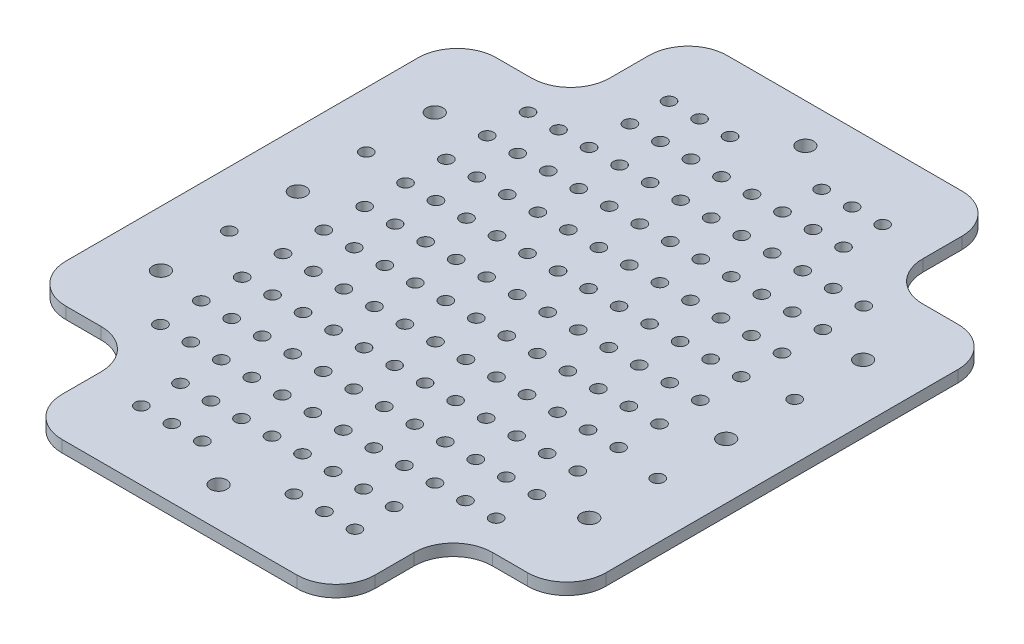
SolidWorks part; units mm, degrees
ref_plane "Front Plane" through (0, 0, 0) normal (0, 0, 1) x (1, 0, 0)
ref_plane "Top Plane" through (0, 0, 0) normal (0, 1, 0) x (1, 0, 0)
ref_plane "Right Plane" through (0, 0, 0) normal (1, 0, 0) x (0, 0, -1)
sketch "Sketch1" plane through (0, 0, 0) normal (0, 1, 0) x (1, 0, 0)
  line L1 (0, 0) -> (138, 0)
  line L2 (0, 0) -> (0, 170)
  line L3 (0, 170) -> (138, 170)
  line L4 (138, 0) -> (138, 170)
  dimension "D1" = 138
  dimension "D2" = 170
extrude "Boss-Extrude1" add sketch "Sketch1" along normal blind 3
sketch "Sketch2" plane through (0, 3, 0) normal (0, 1, 0) x (1, 0, 0)
  line L0 (0, 132) -> (138, 132) construction
  line L1 (0, 170) -> (29, 170)
  line L2 (0, 170) -> (0, 140)
  line L3 (0, 140) -> (29, 140)
  line L4 (29, 170) -> (29, 140)
  line L5 (138, 170) -> (109, 170)
  line L6 (138, 170) -> (138, 140)
  line L7 (138, 140) -> (109, 140)
  line L8 (109, 170) -> (109, 140)
  line L9 (138, 0) -> (109, 0)
  line L10 (138, 0) -> (138, 30)
  line L11 (138, 30) -> (109, 30)
  line L12 (109, 0) -> (109, 30)
  line L13 (0, 0) -> (29, 0)
  line L14 (0, 0) -> (0, 30)
  line L15 (0, 30) -> (29, 30)
  line L16 (29, 0) -> (29, 30)
  line L17 (33.9, 132) -> (41.7, 132) construction
  line L18 (0, 38) -> (138, 38) construction
  line L19 (33.9, 132) -> (33.9, 38) construction
  line L20 (29, 165) -> (109, 165) construction
  line L21 (29, 5) -> (109, 5) construction
  line L22 (69, 165) -> (69, 5) construction
  line L23 (138, 0) -> (138, 170) construction
  line L24 (69, 85) -> (138, 85) construction
  line L25 (0, 170) -> (0, 0) construction
  line L26 (10, 160) -> (10, 10)
  line L27 (10, 10) -> (128, 10)
  line L28 (128, 10) -> (128, 160)
  line L29 (128, 160) -> (10, 160)
  line L30 (10, 160) -> (10, 10) construction
  line L31 (10, 10) -> (128, 10) construction
  line L32 (128, 10) -> (128, 160) construction
  line L33 (128, 160) -> (10, 160) construction
  line L34 (138, 170) -> (0, 170) construction
  line L35 (65.1, 121.5556) -> (72.9, 121.5556) construction
  circle A0 centre (33.9, 132) radius 1.6
  circle A1 centre (41.7, 132) radius 1.6
  circle A2 centre (49.5, 132) radius 1.6
  circle A3 centre (57.3, 132) radius 1.6
  circle A4 centre (65.1, 132) radius 1.6
  circle A5 centre (72.9, 132) radius 1.6
  circle A6 centre (80.7, 132) radius 1.6
  circle A7 centre (88.5, 132) radius 1.6
  circle A8 centre (96.3, 132) radius 1.6
  circle A10 centre (41.7, 121.5556) radius 1.6
  circle A11 centre (49.5, 121.5556) radius 1.6
  circle A12 centre (57.3, 121.5556) radius 1.6
  circle A13 centre (65.1, 121.5556) radius 1.6
  circle A14 centre (72.9, 121.5556) radius 1.6
  circle A15 centre (80.7, 121.5556) radius 1.6
  circle A16 centre (88.5, 121.5556) radius 1.6
  circle A17 centre (96.3, 121.5556) radius 1.6
  circle A19 centre (41.7, 111.1111) radius 1.6
  circle A20 centre (49.5, 111.1111) radius 1.6
  circle A21 centre (57.3, 111.1111) radius 1.6
  circle A22 centre (65.1, 111.1111) radius 1.6
  circle A23 centre (72.9, 111.1111) radius 1.6
  circle A24 centre (80.7, 111.1111) radius 1.6
  circle A25 centre (88.5, 111.1111) radius 1.6
  circle A26 centre (96.3, 111.1111) radius 1.6
  circle A28 centre (41.7, 100.6667) radius 1.6
  circle A29 centre (49.5, 100.6667) radius 1.6
  circle A30 centre (57.3, 100.6667) radius 1.6
  circle A31 centre (65.1, 100.6667) radius 1.6
  circle A32 centre (72.9, 100.6667) radius 1.6
  circle A33 centre (80.7, 100.6667) radius 1.6
  circle A34 centre (88.5, 100.6667) radius 1.6
  circle A35 centre (96.3, 100.6667) radius 1.6
  circle A37 centre (41.7, 90.2222) radius 1.6
  circle A38 centre (49.5, 90.2222) radius 1.6
  circle A39 centre (57.3, 90.2222) radius 1.6
  circle A40 centre (65.1, 90.2222) radius 1.6
  circle A41 centre (72.9, 90.2222) radius 1.6
  circle A42 centre (80.7, 90.2222) radius 1.6
  circle A43 centre (88.5, 90.2222) radius 1.6
  circle A44 centre (96.3, 90.2222) radius 1.6
  circle A46 centre (41.7, 79.7778) radius 1.6
  circle A47 centre (49.5, 79.7778) radius 1.6
  circle A48 centre (57.3, 79.7778) radius 1.6
  circle A49 centre (65.1, 79.7778) radius 1.6
  circle A50 centre (72.9, 79.7778) radius 1.6
  circle A51 centre (80.7, 79.7778) radius 1.6
  circle A52 centre (88.5, 79.7778) radius 1.6
  circle A53 centre (96.3, 79.7778) radius 1.6
  circle A55 centre (41.7, 69.3333) radius 1.6
  circle A56 centre (49.5, 69.3333) radius 1.6
  circle A57 centre (57.3, 69.3333) radius 1.6
  circle A58 centre (65.1, 69.3333) radius 1.6
  circle A59 centre (72.9, 69.3333) radius 1.6
  circle A60 centre (80.7, 69.3333) radius 1.6
  circle A61 centre (88.5, 69.3333) radius 1.6
  circle A62 centre (96.3, 69.3333) radius 1.6
  circle A64 centre (41.7, 58.8889) radius 1.6
  circle A65 centre (49.5, 58.8889) radius 1.6
  circle A66 centre (57.3, 58.8889) radius 1.6
  circle A67 centre (65.1, 58.8889) radius 1.6
  circle A68 centre (72.9, 58.8889) radius 1.6
  circle A69 centre (80.7, 58.8889) radius 1.6
  circle A70 centre (88.5, 58.8889) radius 1.6
  circle A71 centre (96.3, 58.8889) radius 1.6
  circle A73 centre (41.7, 48.4444) radius 1.6
  circle A74 centre (49.5, 48.4444) radius 1.6
  circle A75 centre (57.3, 48.4444) radius 1.6
  circle A76 centre (65.1, 48.4444) radius 1.6
  circle A77 centre (72.9, 48.4444) radius 1.6
  circle A78 centre (80.7, 48.4444) radius 1.6
  circle A79 centre (88.5, 48.4444) radius 1.6
  circle A80 centre (96.3, 48.4444) radius 1.6
  circle A82 centre (41.7, 38) radius 1.6
  circle A83 centre (49.5, 38) radius 1.6
  circle A84 centre (57.3, 38) radius 1.6
  circle A85 centre (65.1, 38) radius 1.6
  circle A86 centre (72.9, 38) radius 1.6
  circle A87 centre (80.7, 38) radius 1.6
  circle A88 centre (88.5, 38) radius 1.6
  circle A89 centre (96.3, 38) radius 1.6
  circle A181 centre (33.9, 121.5556) radius 1.6
  circle A182 centre (33.9, 111.1111) radius 1.6
  circle A183 centre (33.9, 100.6667) radius 1.6
  circle A184 centre (33.9, 90.2222) radius 1.6
  circle A185 centre (33.9, 79.7778) radius 1.6
  circle A186 centre (33.9, 69.3333) radius 1.6
  circle A187 centre (33.9, 58.8889) radius 1.6
  circle A188 centre (33.9, 48.4444) radius 1.6
  circle A189 centre (33.9, 38) radius 1.6
  circle A209 centre (104.1, 132) radius 1.6
  circle A210 centre (104.1, 121.5556) radius 1.6
  circle A211 centre (104.1, 111.1111) radius 1.6
  circle A212 centre (104.1, 100.6667) radius 1.6
  circle A213 centre (104.1, 90.2222) radius 1.6
  circle A214 centre (104.1, 79.7778) radius 1.6
  circle A215 centre (104.1, 69.3333) radius 1.6
  circle A216 centre (104.1, 58.8889) radius 1.6
  circle A217 centre (104.1, 48.4444) radius 1.6
  circle A218 centre (104.1, 38) radius 1.6
  circle A220 centre (69, 160) radius 2.1
  circle A221 centre (69, 10) radius 2.1
  point P220 (69, 121.5556)
  point P225 (69, 170)
  dimension "D4" = 3.2
  dimension "D12" = 4.2
  dimension "D13" = 4.2
  dimension "D1" = 30
  dimension "D2" = 160
  dimension "D5" = 8
  dimension "D8" = 7.8
  dimension "D9" = 30
  dimension "D10" = 80
  dimension "D11" = 8
  dimension "D3" = 10
  dimension "D6" = 10
  dimension "D7" = 10
extrude "Cut-Extrude1" cut sketch "Sketch2" against normal blind 3
sketch "Sketch3" plane through (0, 3, 0) normal (0, 1, 0) x (1, 0, 0)
  line L0 (69, 170) -> (69, 139.75) construction
  line L1 (14.25, 139.75) -> (123.75, 139.75) construction
  line L2 (14.25, 139.75) -> (14.25, 30.25) construction
  line L3 (14.25, 30.25) -> (123.75, 30.25) construction
  line L4 (123.75, 139.75) -> (123.75, 30.25) construction
  line L5 (109, 170) -> (29, 170) construction
  line L6 (41.7, 142.4444) -> (41.7, 132) construction
  line L7 (14.25, 85) -> (0, 85) construction
  line L8 (0, 140) -> (0, 30) construction
  line L9 (41.7, 132) -> (41.7, 121.5556) construction
  line L10 (41.7, 142.4444) -> (49.5, 142.4444) construction
  line L11 (26.1, 132) -> (33.9, 132) construction
  line L12 (33.9, 132) -> (41.7, 132) construction
  circle A0 centre (14.25, 120) radius 2.1
  circle A1 centre (14.25, 50) radius 2.1
  circle A2 centre (14.25, 85) radius 2.1
  circle A3 centre (123.75, 50) radius 2.1
  circle A4 centre (123.75, 85) radius 2.1
  circle A5 centre (123.75, 120) radius 2.1
  circle A7 centre (41.7, 142.4444) radius 1.6
  circle A8 centre (49.5, 142.4444) radius 1.6
  circle A9 centre (57.3, 142.4444) radius 1.6
  circle A10 centre (65.1, 142.4444) radius 1.6
  circle A11 centre (72.9, 142.4444) radius 1.6
  circle A12 centre (80.7, 142.4444) radius 1.6
  circle A13 centre (88.5, 142.4444) radius 1.6
  circle A14 centre (96.3, 142.4444) radius 1.6
  circle A15 centre (49.5, 152.4444) radius 1.6
  circle A16 centre (57.3, 152.4444) radius 1.6
  circle A17 centre (65.1, 152.4444) radius 1.6 [skipped]
  circle A18 centre (72.9, 152.4444) radius 1.6 [skipped]
  circle A19 centre (80.7, 152.4444) radius 1.6
  circle A20 centre (88.5, 152.4444) radius 1.6
  circle A21 centre (96.3, 152.4444) radius 1.6
  circle A22 centre (41.7, 152.4444) radius 1.6
  circle A23 centre (96.3, 27.5556) radius 1.6
  circle A24 centre (88.5, 27.5556) radius 1.6
  circle A25 centre (80.7, 27.5556) radius 1.6
  circle A26 centre (72.9, 27.5556) radius 1.6
  circle A27 centre (65.1, 27.5556) radius 1.6
  circle A28 centre (57.3, 27.5556) radius 1.6
  circle A29 centre (49.5, 27.5556) radius 1.6
  circle A30 centre (41.7, 27.5556) radius 1.6
  circle A31 centre (41.7, 17.5556) radius 1.6
  circle A32 centre (96.3, 17.5556) radius 1.6
  circle A33 centre (88.5, 17.5556) radius 1.6
  circle A34 centre (80.7, 17.5556) radius 1.6
  circle A35 centre (57.3, 17.5556) radius 1.6
  circle A36 centre (49.5, 17.5556) radius 1.6
  circle A37 centre (26.1, 132) radius 1.6
  circle A38 centre (26.1, 121.56) radius 1.6
  circle A39 centre (26.1, 111.12) radius 1.6
  circle A40 centre (26.1, 100.68) radius 1.6
  circle A41 centre (26.1, 90.24) radius 1.6
  circle A42 centre (26.1, 79.8) radius 1.6
  circle A43 centre (26.1, 69.36) radius 1.6
  circle A44 centre (26.1, 58.92) radius 1.6
  circle A45 centre (26.1, 48.48) radius 1.6
  circle A46 centre (26.1, 38.04) radius 1.6
  circle A47 centre (111.9, 132) radius 1.6
  circle A48 centre (111.9, 48.48) radius 1.6
  circle A49 centre (111.9, 58.92) radius 1.6
  circle A50 centre (111.9, 69.36) radius 1.6
  circle A51 centre (111.9, 79.8) radius 1.6
  circle A52 centre (111.9, 90.24) radius 1.6
  circle A53 centre (111.9, 100.68) radius 1.6
  circle A54 centre (111.9, 111.12) radius 1.6
  circle A55 centre (111.9, 121.56) radius 1.6
  circle A56 centre (111.9, 38.04) radius 1.6
  circle A57 centre (14.25, 102.5) radius 1.6
  circle A58 centre (14.25, 67.5) radius 1.6
  circle A59 centre (123.75, 67.5) radius 1.6
  circle A60 centre (123.75, 102.5) radius 1.6
  dimension "D3" = 4.2
  dimension "D4" = 35
  dimension "D6" = 3.2
  dimension "D7" = 8
  dimension "D10" = 2
  dimension "D13" = 17.5
  dimension "D1" = 109.5
  dimension "D2" = 109.5
  dimension "D5" = 35
  dimension "D8" = 7.8
  dimension "D9" = 10
  dimension "D11" = 10.44
  dimension "D14" = 17.5
  dimension "D12" = 10
extrude "Cut-Extrude2" cut sketch "Sketch3" against normal through all
fillet "Fillet1" radius 10 12 edges at (29, 1.5, -170) (29, 1.5, -140) (0, 1.5, -140) (0, 1.5, -30) (29, 1.5, -30) (29, 1.5, 0) (109, 1.5, 0) (109, 1.5, -30) (138, 1.5, -30) (109, 1.5, -140) (138, 1.5, -140) (109, 1.5, -170)
